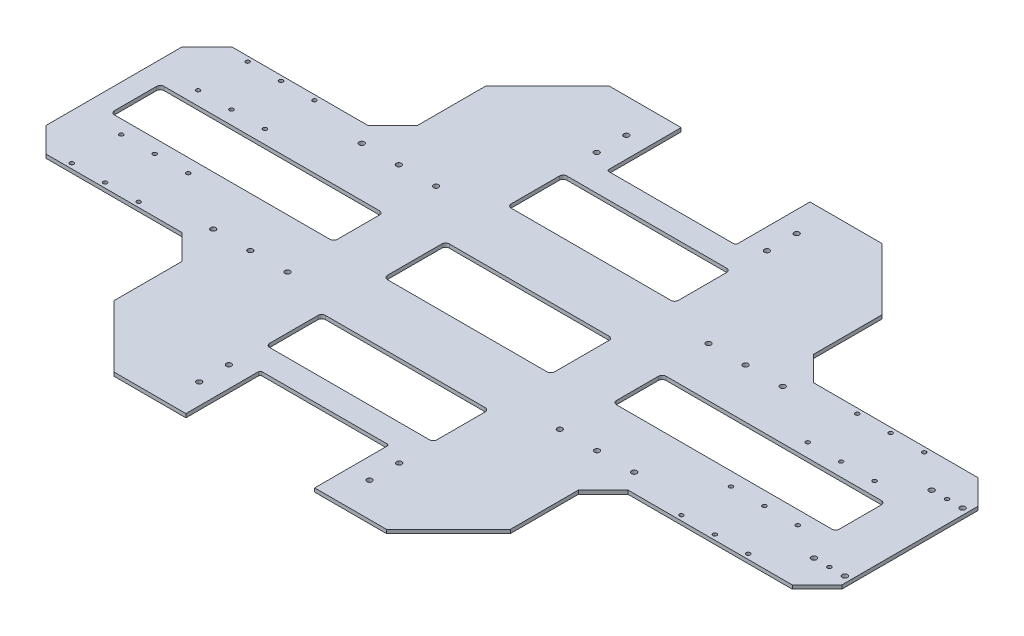
SolidWorks part; units mm, degrees
material "6061-O (SS)"
ref_plane "前视基准面" through (0, 0, 0) normal (0, 0, 1) x (1, 0, 0)
ref_plane "上视基准面" through (0, 0, 0) normal (0, 1, 0) x (1, 0, 0)
ref_plane "右视基准面" through (0, 0, 0) normal (1, 0, 0) x (0, 0, -1)
sketch "草图1" plane through (0, 0, 0) normal (0, 1, 0) x (1, 0, 0)
  line L0 (0, 0) -> (160, -38.7097) construction
  line L1 (-260, 200) -> (260, 200) construction
  line L2 (-260, 200) -> (-260, -200) construction
  line L3 (-260, -200) -> (260, -200) construction
  line L4 (260, 200) -> (260, -200) construction
  line L5 (-260, 200) -> (-160, 123.0769) construction
  line L6 (-260, -200) -> (-160, -123.0769) construction
  line L7 (-310, -75) -> (-160, -75)
  line L8 (-310, -75) -> (-310, 75)
  line L9 (-310, 75) -> (-160, 75)
  line L10 (310, -75) -> (310, 75)
  line L11 (-310, -75) -> (160, 38.7097) construction
  line L12 (-310, 75) -> (-160, 38.7097) construction
  line L13 (-160, -200) -> (160, -200)
  line L14 (-160, -200) -> (-160, -75)
  line L15 (-160, 200) -> (160, 200)
  line L16 (160, -200) -> (160, -75)
  line L17 (-60, -75) -> (0, 0) construction
  line L18 (0, 0) -> (60, -75) construction
  line L19 (-160, 75) -> (-160, 200)
  line L22 (160, 75) -> (310, 75)
  line L24 (97.5, 75) -> (260, 200) construction
  line L25 (160, 75) -> (160, 200)
  line L26 (260, 62.9032) -> (310, 75) construction
  line L27 (260, -62.9032) -> (310, -75) construction
  line L28 (160, -75) -> (310, -75)
  line L29 (160, -123.0769) -> (260, -200) construction
  point P0 (0, 0)
  point P6 (0, 0)
  point P11 (0, 0)
  dimension "D1" = 520
  dimension "D2" = 400
  dimension "D3" = 50
  dimension "D4" = 125
  dimension "D5" = 100
extrude "凸台-拉伸1" add sketch "草图1" along normal blind 3
chamfer "倒角1" distance 20 angle 45 8 edges at (-160, 1.5, -75) (-310, 1.5, -75) (-310, 1.5, 75) (-160, 1.5, 75) (160, 1.5, 75) (160, 1.5, -75) (310, 1.5, 75) (310, 1.5, -75)
chamfer "倒角2" distance 50 angle 45 4 edges at (160, 1.5, 200) (-160, 1.5, 200) (160, 1.5, -200) (-160, 1.5, -200)
sketch "草图2" plane through (0, 0, 0) normal (0, -1, 0) x (-1, 0, 0)
  line L1 (52, -140) -> (-52, -140)
  line L2 (52, -140) -> (52, -233.0888)
  line L3 (52, -233.0888) -> (-52, -233.0888)
  line L4 (-52, -140) -> (-52, -233.0888)
  line L6 (0, 0) -> (119.8246, 0) construction
  line L7 (-52, 140) -> (-52, 233.0888)
  line L8 (52, 233.0888) -> (-52, 233.0888)
  line L9 (52, 140) -> (52, 233.0888)
  line L10 (52, 140) -> (-52, 140)
  line L11 (160, -95) -> (160, -150) construction
  line L12 (-160, -150) -> (-160, -95) construction
  dimension "D1" = 108
  dimension "D2" = 108
extrude "切除-拉伸1" cut sketch "草图2" against normal blind 40
fillet "圆角1" radius 1.5 4 edges at (-52, 1.5, -140) (52, 1.5, -140) (52, 1.5, 140) (-52, 1.5, 140)
sketch "草图3" plane through (0, 0, 0) normal (0, -1, 0) x (1, 0, 0)
  circle A0 centre (-68.75, 172.5) radius 2.1
  circle A1 centre (-68.75, 148.5) radius 2.1
  circle A2 centre (68.75, 172.5) radius 2.1
  circle A3 centre (68.75, 148.5) radius 2.1
  circle A4 centre (-68.75, -148.5) radius 2.1
  circle A5 centre (-68.75, -172.5) radius 2.1
  circle A6 centre (68.75, -148.5) radius 2.1
  circle A7 centre (68.75, -172.5) radius 2.1
extrude "切除-拉伸2" cut sketch "草图3" against normal blind 80
sketch "草图4" plane through (0, 0, 0) normal (0, -1, 0) x (1, 0, 0)
  line L0 (0, 0) -> (124.2092, 0) construction
  line L1 (0, 0) -> (0, 63.2758) construction
  circle A0 centre (273.2002, 71) radius 1.6
  circle A1 centre (273.2002, 30.9984) radius 1.6
  circle A2 centre (246.2002, 71) radius 1.6
  circle A3 centre (219.2002, 71) radius 1.6
  circle A4 centre (246.2002, 30.9984) radius 1.6
  circle A5 centre (219.2002, 30.9984) radius 1.6
  circle A6 centre (110, 60) radius 2.1
  circle A7 centre (140, 60) radius 2.1
  circle A8 centre (170, 60) radius 2.1
  circle A9 centre (170, -60) radius 2.1
  circle A10 centre (140, -60) radius 2.1
  circle A11 centre (110, -60) radius 2.1
  circle A12 centre (219.2002, -30.9984) radius 1.6
  circle A13 centre (246.2002, -30.9984) radius 1.6
  circle A14 centre (219.2002, -71) radius 1.6
  circle A15 centre (246.2002, -71) radius 1.6
  circle A16 centre (273.2002, -30.9984) radius 1.6
  circle A17 centre (273.2002, -71) radius 1.6
  circle A18 centre (-273.2002, -71) radius 1.6
  circle A19 centre (-273.2002, -30.9984) radius 1.6
  circle A20 centre (-246.2002, -71) radius 1.6
  circle A21 centre (-219.2002, -71) radius 1.6
  circle A22 centre (-246.2002, -30.9984) radius 1.6
  circle A23 centre (-219.2002, -30.9984) radius 1.6
  circle A24 centre (-110, -60) radius 2.1
  circle A25 centre (-140, -60) radius 2.1
  circle A26 centre (-170, -60) radius 2.1
  circle A27 centre (-170, 60) radius 2.1
  circle A28 centre (-140, 60) radius 2.1
  circle A29 centre (-110, 60) radius 2.1
  circle A30 centre (-219.2002, 30.9984) radius 1.6
  circle A31 centre (-246.2002, 30.9984) radius 1.6
  circle A32 centre (-219.2002, 71) radius 1.6
  circle A33 centre (-246.2002, 71) radius 1.6
  circle A34 centre (-273.2002, 30.9984) radius 1.6
  circle A35 centre (-273.2002, 71) radius 1.6
extrude "切除-拉伸3" cut sketch "草图4" against normal blind 29
sketch "草图5" plane through (0, 0, 0) normal (0, -1, 0) x (1, 0, 0)
  line L0 (310, 55) -> (290, 75) construction
  line L1 (310, 55) -> (310, -55) construction
  line L2 (290, -75) -> (310, -55) construction
  line L3 (310, 55) -> (290, 75)
  line L4 (310, 55) -> (310, -55)
  line L5 (290, -75) -> (310, -55)
  line L6 (290, -75) -> (312.7002, -75)
  line L7 (312.7002, -75) -> (332.7002, -55)
  line L9 (332.7002, -55) -> (332.7002, 55)
  line L10 (332.7002, 55) -> (312.7002, 75)
  line L11 (312.7002, 75) -> (290, 75)
extrude "凸台-拉伸2" add sketch "草图5" against normal blind 3
sketch "草图6" plane through (0, 0, 0) normal (0, -1, 0) x (1, 0, 0)
  circle A0 centre (302.7002, 47.5) radius 2.15
  circle A1 centre (327.7002, 47.5) radius 2.15
  circle A2 centre (327.7002, -47.5) radius 2.15
  circle A3 centre (302.7002, -47.5) radius 2.15
  dimension "D1" = 4.3
extrude "切除-拉伸4" cut sketch "草图6" against normal blind 3
sketch "草图7" plane through (0, 0, 0) normal (0, -1, 0) x (1, 0, 0)
  line L0 (180, 75) -> (312.7002, 75) construction
  line L1 (289.7002, -20) -> (115.7002, -20)
  line L2 (292.7002, -17) -> (292.7002, 17)
  line L3 (289.7002, 20) -> (115.7002, 20)
  line L4 (112.7002, -17) -> (112.7002, 17)
  line L5 (64.7002, -25) -> (-64.3251, -25)
  line L6 (67.7002, -22) -> (67.7002, 22)
  line L7 (64.7002, 25) -> (-64.3251, 25)
  line L8 (-67.3251, -22) -> (-67.3251, 22)
  line L9 (64.7002, -120) -> (-64.3251, -120)
  line L10 (67.7002, -117) -> (67.7002, -78)
  line L11 (64.7002, -75) -> (-64.3251, -75)
  line L12 (-67.3251, -117) -> (-67.3251, -78)
  line L13 (312.7002, -75) -> (180, -75) construction
  line L23 (45.4531, 0) -> (0, 0) construction
  line L24 (0, 0) -> (0, 77.4247) construction
  line L25 (-112.7002, -17) -> (-112.7002, 17)
  line L26 (-289.7002, 20) -> (-115.7002, 20)
  line L27 (-292.7002, -17) -> (-292.7002, 17)
  line L28 (-289.7002, -20) -> (-115.7002, -20)
  line L29 (-67.3251, 117) -> (-67.3251, 78)
  line L30 (64.7002, 75) -> (-64.3251, 75)
  line L31 (67.7002, 117) -> (67.7002, 78)
  line L32 (64.7002, 120) -> (-64.3251, 120)
  arc A0 (289.7002, -20) -> (292.7002, -17) centre (289.7002, -17) ccw
  arc A1 (292.7002, 17) -> (289.7002, 20) centre (289.7002, 17) ccw
  arc A2 (115.7002, -20) -> (112.7002, -17) centre (115.7002, -17) cw
  arc A3 (115.7002, 20) -> (112.7002, 17) centre (115.7002, 17) ccw
  arc A4 (64.7002, -120) -> (67.7002, -117) centre (64.7002, -117) ccw
  arc A5 (-64.3251, -120) -> (-67.3251, -117) centre (-64.3251, -117) cw
  arc A6 (-64.3251, -75) -> (-67.3251, -78) centre (-64.3251, -78) ccw
  arc A7 (67.7002, -78) -> (64.7002, -75) centre (64.7002, -78) ccw
  arc A8 (64.7002, -25) -> (67.7002, -22) centre (64.7002, -22) ccw
  arc A9 (67.7002, 22) -> (64.7002, 25) centre (64.7002, 22) ccw
  arc A10 (-64.3251, -25) -> (-67.3251, -22) centre (-64.3251, -22) cw
  arc A11 (-64.3251, 25) -> (-67.3251, 22) centre (-64.3251, 22) ccw
  arc A12 (-115.7002, 20) -> (-112.7002, 17) centre (-115.7002, 17) cw
  arc A13 (-115.7002, -20) -> (-112.7002, -17) centre (-115.7002, -17) ccw
  arc A14 (-292.7002, 17) -> (-289.7002, 20) centre (-289.7002, 17) cw
  arc A15 (-289.7002, -20) -> (-292.7002, -17) centre (-289.7002, -17) cw
  arc A16 (67.7002, 78) -> (64.7002, 75) centre (64.7002, 78) cw
  arc A17 (-64.3251, 75) -> (-67.3251, 78) centre (-64.3251, 78) cw
  arc A18 (-64.3251, 120) -> (-67.3251, 117) centre (-64.3251, 117) ccw
  arc A19 (64.7002, 120) -> (67.7002, 117) centre (64.7002, 117) cw
  point P46 (-67.3251, -120)
  point P49 (-67.3251, -75)
  dimension "D13" = 3
  dimension "D1" = 55
  dimension "D2" = 55
  dimension "D12" = 45
extrude "切除-拉伸5" cut sketch "草图7" against normal blind 15
sketch "草图8" plane through (0, 0, 0) normal (0, -1, 0) x (1, 0, 0)
  circle A17 centre (315.2002, 47.5) radius 1.6
  circle A18 centre (315.2002, -47.5) radius 1.6
extrude "切除-拉伸6" cut sketch "草图8" against normal blind 15
